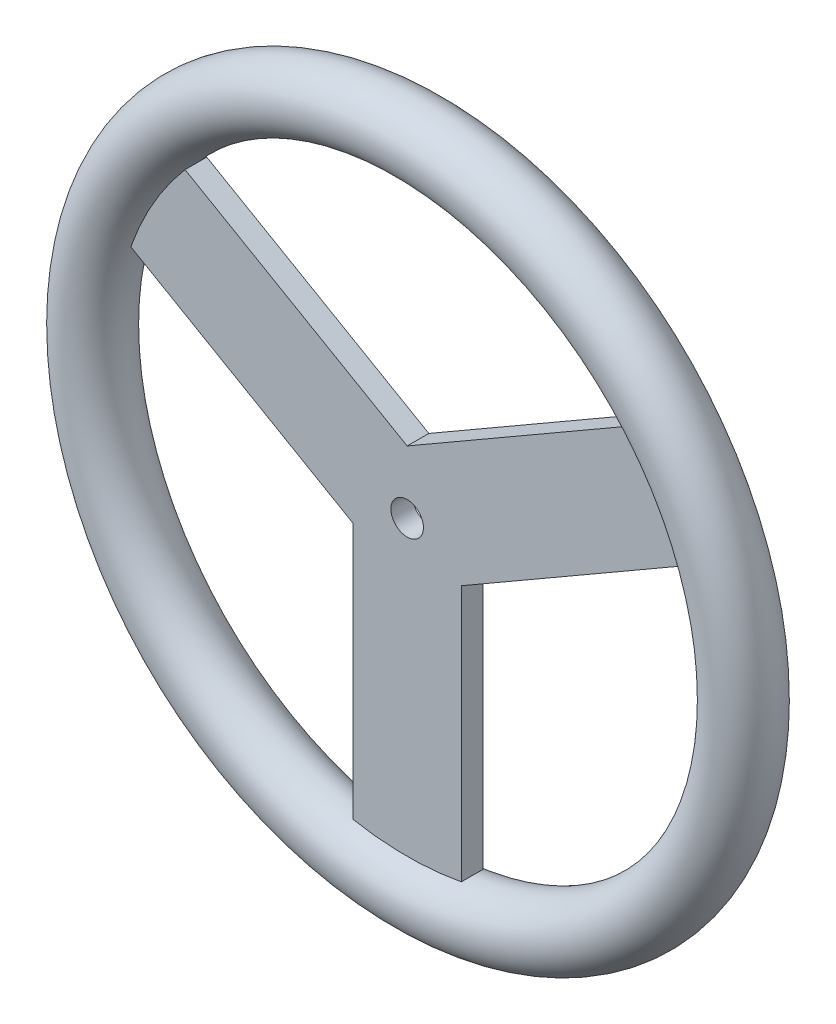
SolidWorks part; units mm, degrees
ref_plane "Ön Düzlem" through (0, 0, 0) normal (0, 0, 1) x (1, 0, 0)
ref_plane "Üst Düzlem" through (0, 0, 0) normal (0, 1, 0) x (1, 0, 0)
ref_plane "Sağ Düzlem" through (0, 0, 0) normal (1, 0, 0) x (0, 0, -1)
sketch "Çizim1" plane through (0, 0, 0) normal (0, 0, 1) x (1, 0, 0)
  line L0 (-150, 0) -> (150, 0) construction
  arc A0 (150, 0) -> (-150, 0) centre (0, 0) ccw
  dimension "D1" = 300
sketch "Çizim3" plane through (0, 0, 0) normal (0, 1, 0) x (1, 0, 0)
  line L0 (-150, 0) -> (150, 0) construction
  circle A0 centre (-150, 0) radius 15
  dimension "D1" = 30
sweep "Süpür2" add profiles "Çizim3" path "Çizim1"
mirror "Aynalama1" about plane through (150, 0, 0) normal (0, -1, 0) of "Süpür2"
sketch "Çizim5" plane through (0, 0, 0) normal (0, 0, 1) x (1, 0, 0)
  line L0 (0, 0) -> (-116.9134, 67.5) construction
  line L1 (0, 0) -> (116.9134, 67.5) construction
  line L2 (0, 0) -> (0, -135) construction
  line L3 (-102.3913, 87.9831) -> (0, 28.8675)
  line L4 (0, 28.8675) -> (102.3913, 87.9831)
  line L5 (-127.3913, 44.6819) -> (-25, -14.4338)
  line L6 (-25, -14.4338) -> (-25, -132.665)
  line L7 (127.3913, 44.6819) -> (25, -14.4338)
  line L8 (25, -14.4338) -> (25, -132.665)
  circle A0 centre (0, 0) radius 135 construction
  arc A1 (-25, -132.665) -> (25, -132.665) centre (0, 0) ccw
  arc A2 (-102.3913, 87.9831) -> (-127.3913, 44.6819) centre (0, 0) ccw
  arc A3 (127.3913, 44.6819) -> (102.3913, 87.9831) centre (0, 0) ccw
  dimension "D1" = 120
  dimension "D2" = 120
  dimension "D3" = 50
  dimension "D4" = 50
  dimension "D5" = 50
  dimension "D6" = 25
  dimension "D7" = 25
  dimension "D8" = 25
extrude "Yükseklik-Ekstrüzyon1" add sketch "Çizim5" along normal blind 5 and the other way blind 5 separate body
sketch "Çizim6" plane through (0, 0, 5) normal (0, 0, 1) x (1, 0, 0)
  circle A0 centre (0, 0) radius 7.5
  dimension "D1" = 15
extrude "Kes-Ekstrüzyon1" cut sketch "Çizim6" against normal blind 201 and the other way blind 128
